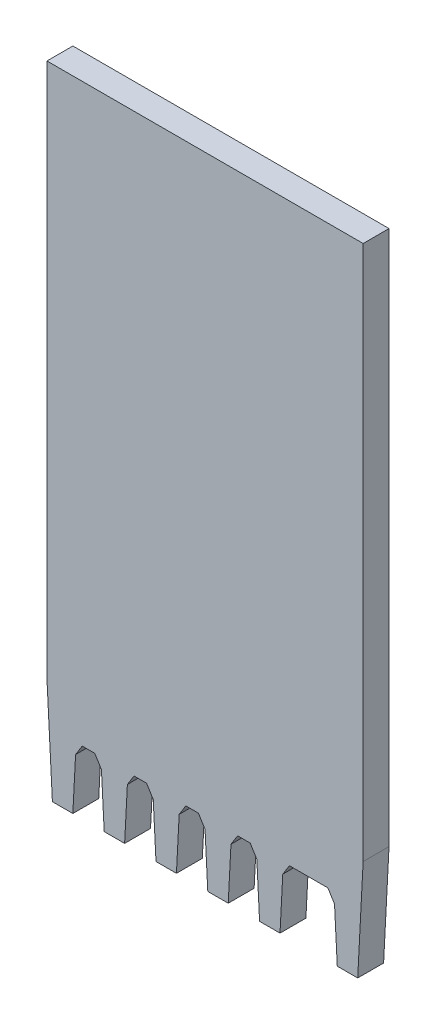
SolidWorks part; units mm, degrees
ref_plane "Front Plane" through (0, 0, 0) normal (0, 0, 1) x (1, 0, 0)
ref_plane "Top Plane" through (0, 0, 0) normal (0, 1, 0) x (1, 0, 0)
ref_plane "Right Plane" through (0, 0, 0) normal (1, 0, 0) x (0, 0, -1)
sketch "Sketch1" plane through (0, 0, 0) normal (0, 0, 1) x (1, 0, 0)
  line L0 (0, 0) -> (0, 37) construction
  line L1 (0, 37) -> (18.3124, 37) construction
  line L2 (18.3124, 37) -> (18.3124, 0) construction
  line L3 (18.3124, 0) -> (0, 0) construction
  line L4 (0, 3) -> (18.3124, 3) construction
  line L5 (0, 6) -> (18.3124, 6) construction
  line L6 (0.9062, 6) -> (0.9062, 0) construction
  line L7 (3.9062, 6) -> (3.9062, 0) construction
  line L8 (6.9062, 6) -> (6.9062, 0) construction
  line L9 (9.9062, 6) -> (9.9062, 0) construction
  line L10 (12.9062, 6) -> (12.9062, 0) construction
  line L11 (17.4062, 6) -> (17.4062, 0) construction
  line L12 (0.9062, 3) -> (3.9062, 3) construction
  line L13 (3.9062, 3) -> (6.9062, 3) construction
  line L14 (6.9062, 3) -> (9.9062, 3) construction
  line L15 (9.9062, 3) -> (12.9062, 3) construction
  line L16 (12.9062, 3) -> (17.4062, 3) construction
  line L17 (0.9062, 3) -> (0, 3) construction
  line L18 (17.4062, 3) -> (18.3124, 3) construction
  line L19 (2.4062, 3) -> (2.4062, 0) construction
  line L20 (5.4062, 3) -> (5.4062, 0) construction
  line L21 (8.4062, 3) -> (8.4062, 0) construction
  line L22 (11.4062, 3) -> (11.4062, 0) construction
  line L23 (15.1562, 3) -> (15.1562, 0) construction
  line L24 (14.4062, 3.75) -> (15.9062, 3.75) construction
  line L25 (0, 6) -> (0.3144, 0)
  line L26 (0.3144, 0) -> (1.4979, 0)
  line L27 (1.4979, 0) -> (1.6572, 3.0393)
  line L28 (3.1552, 3.0393) -> (3.3144, 0)
  line L29 (3.3144, 0) -> (4.4979, 0)
  line L30 (4.4979, 0) -> (4.6572, 3.0393)
  line L31 (6.1552, 3.0393) -> (6.3144, 0)
  line L32 (6.3144, 0) -> (7.4979, 0)
  line L33 (7.4979, 0) -> (7.6572, 3.0393)
  line L34 (9.1552, 3.0393) -> (9.3144, 0)
  line L35 (9.3144, 0) -> (10.4979, 0)
  line L36 (10.4979, 0) -> (10.6572, 3.0393)
  line L37 (12.1552, 3.0393) -> (12.3144, 0)
  line L38 (12.3144, 0) -> (13.4979, 0)
  line L39 (13.4979, 0) -> (13.6572, 3.0393)
  line L40 (16.6552, 3.0393) -> (16.8144, 0)
  line L41 (16.8144, 0) -> (17.9979, 0)
  line L42 (17.9979, 0) -> (18.3124, 6)
  line L44 (1.6572, 3.0393) -> (2.0426, 3.656)
  line L45 (0, 6) -> (0, 37)
  line L46 (0, 37) -> (18.3124, 37)
  line L47 (18.3124, 37) -> (18.3124, 6)
  line L48 (9.1562, 37) -> (9.1562, 6) construction
  line L49 (2.0426, 3.656) -> (2.7698, 3.656)
  line L50 (2.7698, 3.656) -> (3.1552, 3.0393)
  line L51 (4.6572, 3.0393) -> (5.0426, 3.656)
  line L52 (5.0426, 3.656) -> (5.7698, 3.656)
  line L53 (5.7698, 3.656) -> (6.1552, 3.0393)
  line L54 (7.6572, 3.0393) -> (8.0426, 3.656)
  line L55 (8.0426, 3.656) -> (8.7698, 3.656)
  line L56 (8.7698, 3.656) -> (9.1552, 3.0393)
  line L57 (10.6572, 3.0393) -> (11.0426, 3.656)
  line L58 (11.0426, 3.656) -> (11.7698, 3.656)
  line L59 (11.7698, 3.656) -> (12.1552, 3.0393)
  line L60 (13.6572, 3.0393) -> (14.0426, 3.656)
  line L61 (14.0426, 3.656) -> (16.2698, 3.656)
  line L62 (16.2698, 3.656) -> (16.6552, 3.0393)
  arc A0 (3.1552, 3.0393) -> (1.6572, 3.0393) centre (2.4062, 3) ccw construction
  arc A1 (6.1552, 3.0393) -> (4.6572, 3.0393) centre (5.4062, 3) ccw construction
  arc A2 (9.1552, 3.0393) -> (7.6572, 3.0393) centre (8.4062, 3) ccw construction
  arc A3 (12.1552, 3.0393) -> (10.6572, 3.0393) centre (11.4062, 3) ccw construction
  arc A4 (13.6572, 3.0393) -> (14.4062, 3.75) centre (14.4062, 3) cw construction
  arc A5 (16.6552, 3.0393) -> (15.9062, 3.75) centre (15.9062, 3) ccw construction
  dimension "D7" = 0.75
  dimension "D1" = 3
  dimension "D2" = 6
  dimension "D3" = 31
  dimension "D4" = 3
  dimension "D6" = 4.5
  dimension "D8" = 3
  dimension "D9" = 18.3124
  dimension "D10" = 37
extrude "Boss-Extrude1" add sketch "Sketch1" along normal blind 1.5
sketch "Sketch3" plane through (0, 0, 0) normal (0, 0, 1) x (1, 0, 0)
  line L0 (-0.4005, 6) -> (18.7129, 6)
  line L1 (18.7129, 3) -> (-0.4005, 3) construction
  line L2 (-0.4005, 0) -> (18.7129, 0) construction
  line L3 (-0.4005, -0.5) -> (18.7129, -0.5) construction
  line L4 (18.7129, -0.5) -> (18.7129, 6) construction
  line L5 (-0.4005, 6) -> (-0.4005, -0.5) construction
  line L6 (18.3124, 0) -> (0, 0) construction
  line L7 (0, 3) -> (18.3124, 3) construction
  line L8 (0, 6) -> (18.3124, 6) construction
  line L9 (0.3407, -0.5) -> (0, 6) construction
  line L10 (18.3124, 6) -> (17.9717, -0.5) construction
  line L11 (17.9979, 0) -> (18.3124, 6) construction
  line L12 (0, 6) -> (0.3144, 0) construction
  line L13 (5.4062, 6) -> (5.4062, -0.5) construction
  line L14 (3.9062, 6) -> (3.9062, -0.5) construction
  line L15 (5.4062, 3) -> (5.4062, 0) construction
  line L16 (3.1572, 3) -> (3.3407, -0.5) construction
  line L17 (2.7567, 3) -> (2.9401, -0.5)
  line L18 (3.1552, 3.0393) -> (3.3144, 0) construction
  line L19 (2.9401, -0.5) -> (4.8723, -0.5)
  line L20 (4.8723, -0.5) -> (5.0557, 3)
  line L21 (2.8484, 1.25) -> (3.2478, 1.2709) construction
  line L22 (5.9401, -0.5) -> (5.7567, 3)
  line L26 (7.8723, -0.5) -> (5.9401, -0.5)
  line L27 (8.0557, 3) -> (7.8723, -0.5)
  line L30 (2.4062, -0.5) -> (2.4062, 6) construction
  line L31 (2.4062, 3) -> (2.4062, 0) construction
  line L32 (8.4062, 6) -> (8.4062, -0.5) construction
  line L34 (11.4062, -0.5) -> (11.4062, 6) construction
  line L35 (15.1562, -0.5) -> (15.1562, 6) construction
  line L36 (8.4062, 3) -> (8.4062, 0) construction
  line L37 (11.4062, 3) -> (11.4062, 0) construction
  line L38 (15.1562, 3) -> (15.1562, 0) construction
  line L39 (10.8723, -0.5) -> (11.0557, 3)
  line L40 (8.9401, -0.5) -> (10.8723, -0.5)
  line L41 (8.7567, 3) -> (8.9401, -0.5)
  line L42 (11.9401, -0.5) -> (11.7567, 3)
  line L43 (13.8723, -0.5) -> (11.9401, -0.5)
  line L44 (14.0557, 3) -> (13.8723, -0.5)
  line L45 (16.4401, -0.5) -> (18.3723, -0.5)
  line L46 (16.2567, 3) -> (16.4401, -0.5)
  line L47 (18.3723, -0.5) -> (18.7129, 6)
  line L48 (1.8723, -0.5) -> (-0.0599, -0.5)
  line L49 (2.0557, 3) -> (1.8723, -0.5)
  line L50 (-0.0599, -0.5) -> (-0.4005, 6)
  line L51 (16.2567, 3) -> (14.0557, 3)
  line L52 (11.7567, 3) -> (11.0557, 3)
  line L53 (8.7567, 3) -> (8.0557, 3)
  line L54 (5.7567, 3) -> (5.0557, 3)
  line L55 (2.7567, 3) -> (2.0557, 3)
  dimension "D1" = 0.5
  dimension "D2" = 0.4
ref_plane "Plane1" through (3.9062, 0, 0) normal (1, 0, 0) x (0, 0, -1)
sketch "Sketch4" plane through (3.9062, 0, 0) normal (1, 0, 0) x (0, 0, -1)
  line L0 (0, 6) -> (0, -0.5) construction
  line L1 (0.6, 6) -> (-2.1, 6) construction
  line L2 (0.6, 6) -> (0.6, -0.5) construction
  line L3 (0.6, -0.5) -> (-2.1, -0.5) construction
  line L4 (-2.1, 6) -> (-2.1, -0.5) construction
  line L5 (-0.75, -0.5) -> (-0.75, 6) construction
  line L6 (-1.5, 6) -> (-1.5, -0.5) construction
  line L7 (0.6, 2.4005) -> (-2.1, 2.4005) construction
  line L8 (0.3, 6) -> (0.3, -0.5) construction
  line L9 (0.6, 2.4005) -> (3.846, 6) construction
  line L10 (2.2302, 6) -> (0.6, 4.1923) construction
  line L11 (0.6, 4.1923) -> (1.7139, 3.1878) construction
  line L12 (1.7139, 3.1878) -> (4.25, 6)
  line L13 (4.25, 6) -> (0.6, 6) construction
  line L14 (0.3, 1) -> (-1.8, 1) construction
  line L15 (-2.1, 0) -> (0.6, 0) construction
  line L16 (1.7139, 3.1878) -> (1.4912, 3.3887)
  line L17 (1.4912, 3.3887) -> (0.6, 2.4005)
  line L18 (-3.2139, 3.1878) -> (-5.75, 6)
  line L19 (-3.2139, 3.1878) -> (-2.9912, 3.3887)
  line L20 (-2.9912, 3.3887) -> (-2.1, 2.4005)
  line L21 (-2.1, 6) -> (-5.75, 6) construction
  line L22 (0.6, 3.0724) -> (3.2401, 6) construction
  arc A0 (0.4965, 2.2224) -> (0.6, -0.5) centre (4.2, 1) ccw
  arc A1 (0.6, 2.4005) -> (0.4965, 2.2224) centre (0.9713, 2.0656) ccw
  arc A2 (-2.1, 2.4005) -> (-1.9965, 2.2224) centre (-2.4713, 2.0656) cw
  arc A3 (-1.9965, 2.2224) -> (-2.1, -0.5) centre (-5.7, 1) cw
  dimension "D6" = 0.5
  dimension "D1" = 0.6
  dimension "D2" = 0.3
  dimension "D3" = 1.5
  dimension "D4" = 1
  dimension "D5" = 0.3
  dimension "D7" = 10
sketch "Sketch5" plane through (0, 0, 0) normal (1, 0, 0) x (0, 0, -1)
  line L0 (2.2302, 6) -> (0.6, 4.1923) construction
  line L1 (0.6, 4.1923) -> (1.7139, 3.1878) construction
  line L2 (1.7139, 3.1878) -> (4.25, 6) construction
  line L3 (2.2302, 6) -> (0.6, 4.1923) construction
  line L4 (0.6, 4.1923) -> (1.7139, 3.1878) construction
  line L5 (1.7139, 3.1878) -> (4.25, 6) construction
ref_plane "Plane2" through (0, 2.6105, -2.3541) normal (0, 0.7426, -0.6697) x (1, 0, 0)
sketch "Sketch6" plane through (0, 2.6105, -2.3541) normal (0, 0.7426, -0.6697) x (1, 0, 0)
  line L1 (3.9062, -2.362) -> (3.9062, -0.862) construction
  line L2 (3.9062, -2.362) -> (3.9062, -5.0612) construction
  line L3 (4.6562, -5.0612) -> (3.1562, -5.0612)
  line L4 (4.6562, -1.612) -> (3.1562, -1.612) construction
  line L5 (3.1562, -1.612) -> (3.1562, -5.0612)
  line L6 (4.6562, -1.612) -> (4.6562, -5.0612)
  line L10 (2.4062, -5.0612) -> (15.1562, -5.0612) construction
  line L11 (15.1562, -5.0612) -> (15.1562, -0.862) construction
  line L12 (15.1562, -0.862) -> (2.4062, -0.862) construction
  line L13 (2.4062, -0.862) -> (2.4062, -5.0612) construction
  line L14 (15.1562, 0.3349) -> (15.1562, -4.0182) construction
  line L15 (2.4062, 0.3349) -> (2.4062, -4.0182) construction
  line L16 (11.4062, -5.0612) -> (11.4062, -0.862) construction
  line L17 (8.4062, -5.0612) -> (8.4062, -0.862) construction
  line L18 (5.4062, -5.0612) -> (5.4062, -0.862) construction
  line L19 (5.4062, -4.0182) -> (5.4062, 0.3349) construction
  line L20 (8.4062, -4.0182) -> (8.4062, 0.3349) construction
  line L21 (11.4062, 0.3349) -> (11.4062, -4.0182) construction
  line L22 (0.1562, -1.612) -> (0.1562, -5.0612)
  line L23 (0.1562, -5.0612) -> (1.6562, -5.0612)
  line L24 (1.6562, -1.612) -> (1.6562, -5.0612)
  line L25 (7.6562, -1.612) -> (7.6562, -5.0612)
  line L26 (6.1562, -5.0612) -> (7.6562, -5.0612)
  line L27 (6.1562, -1.612) -> (6.1562, -5.0612)
  line L28 (10.6562, -1.612) -> (10.6562, -5.0612)
  line L29 (10.6562, -5.0612) -> (9.1562, -5.0612)
  line L30 (9.1562, -1.612) -> (9.1562, -5.0612)
  line L31 (13.6562, -1.612) -> (13.6562, -5.0612)
  line L32 (12.1562, -5.0612) -> (13.6562, -5.0612)
  line L33 (12.1562, -1.612) -> (12.1562, -5.0612)
  line L34 (18.1562, -1.612) -> (18.1562, -5.0612)
  line L35 (18.1562, -5.0612) -> (16.6562, -5.0612)
  line L36 (16.6562, -1.612) -> (16.6562, -5.0612)
  circle A0 centre (3.9062, -1.612) radius 0.75 construction
  arc A1 (4.6562, -1.612) -> (3.1562, -1.612) centre (3.9062, -1.612) ccw
  arc A2 (0.1562, -1.612) -> (1.6562, -1.612) centre (0.9062, -1.612) cw
  arc A3 (6.1562, -1.612) -> (7.6562, -1.612) centre (6.9062, -1.612) cw
  arc A4 (10.6562, -1.612) -> (9.1562, -1.612) centre (9.9062, -1.612) ccw
  arc A5 (12.1562, -1.612) -> (13.6562, -1.612) centre (12.9062, -1.612) cw
  arc A6 (18.1562, -1.612) -> (16.6562, -1.612) centre (17.4062, -1.612) ccw
ref_plane "Plane3" through (0, 1.6223, -1.463) normal (0, 0.7426, -0.6697) x (1, 0, 0)
sketch "Sketch7" plane through (0, 1.6223, -1.463) normal (0, 0.7426, -0.6697) x (1, 0, 0)
  line L0 (3.1562, -1.612) -> (3.1562, -5.0612) construction
  line L1 (4.6562, -5.0612) -> (3.1562, -5.0612) construction
  line L2 (4.6562, -1.612) -> (4.6562, -5.0612) construction
  line L3 (3.1562, -1.612) -> (3.1562, -5.0612) construction
  line L4 (4.6562, -5.0612) -> (3.1562, -5.0612) construction
  line L5 (4.6562, -1.612) -> (4.6562, -5.0612) construction
  line L6 (3.9062, -0.862) -> (3.9062, -5.0612) construction
  line L7 (4.6562, -1.612) -> (3.1562, -1.612) construction
  line L8 (4.6562, -2.362) -> (3.1562, -2.362) construction
  line L9 (3.4562, -1.612) -> (3.4562, -2.362)
  line L10 (3.4562, -2.362) -> (4.3562, -2.362)
  line L11 (4.3562, -2.362) -> (4.3562, -1.612)
  line L12 (2.4062, -0.862) -> (2.4062, -5.0612) construction
  line L13 (2.4062, -5.0612) -> (15.1562, -5.0612) construction
  line L14 (15.1562, -0.862) -> (2.4062, -0.862) construction
  line L15 (5.4062, -5.0612) -> (5.4062, -0.862) construction
  line L16 (8.4062, -5.0612) -> (8.4062, -0.862) construction
  line L17 (11.4062, -5.0612) -> (11.4062, -0.862) construction
  line L18 (15.1562, -5.0612) -> (15.1562, -0.862) construction
  line L19 (2.4062, -0.862) -> (2.4062, -5.0612) construction
  line L20 (2.4062, -5.0612) -> (15.1562, -5.0612) construction
  line L21 (15.1562, -0.862) -> (2.4062, -0.862) construction
  line L22 (5.4062, -5.0612) -> (5.4062, -0.862) construction
  line L23 (8.4062, -5.0612) -> (8.4062, -0.862) construction
  line L24 (11.4062, -5.0612) -> (11.4062, -0.862) construction
  line L25 (15.1562, -5.0612) -> (15.1562, -0.862) construction
  line L26 (0.4562, -2.362) -> (0.4562, -1.612)
  line L27 (1.3562, -2.362) -> (0.4562, -2.362)
  line L28 (1.3562, -1.612) -> (1.3562, -2.362)
  line L29 (7.3562, -2.362) -> (6.4562, -2.362)
  line L30 (7.3562, -1.612) -> (7.3562, -2.362)
  line L31 (6.4562, -2.362) -> (6.4562, -1.612)
  line L32 (9.4562, -1.612) -> (9.4562, -2.362)
  line L33 (10.3562, -2.362) -> (10.3562, -1.612)
  line L34 (9.4562, -2.362) -> (10.3562, -2.362)
  line L35 (13.3562, -1.612) -> (13.3562, -2.362)
  line L36 (12.4562, -2.362) -> (12.4562, -1.612)
  line L37 (13.3562, -2.362) -> (12.4562, -2.362)
  line L38 (16.9562, -1.612) -> (16.9562, -2.362)
  line L39 (17.8562, -2.362) -> (17.8562, -1.612)
  line L40 (16.9562, -2.362) -> (17.8562, -2.362)
  arc A0 (4.6562, -1.612) -> (3.1562, -1.612) centre (3.9062, -1.612) ccw construction
  arc A1 (4.6562, -1.612) -> (3.1562, -1.612) centre (3.9062, -1.612) ccw construction
  circle A2 centre (3.9062, -1.612) radius 0.45 construction
  arc A3 (4.3562, -1.612) -> (3.4562, -1.612) centre (3.9062, -1.612) ccw
  arc A4 (0.4562, -1.612) -> (1.3562, -1.612) centre (0.9062, -1.612) cw
  arc A5 (6.4562, -1.612) -> (7.3562, -1.612) centre (6.9062, -1.612) cw
  arc A6 (10.3562, -1.612) -> (9.4562, -1.612) centre (9.9062, -1.612) ccw
  arc A7 (12.4562, -1.612) -> (13.3562, -1.612) centre (12.9062, -1.612) cw
  arc A8 (17.8562, -1.612) -> (16.9562, -1.612) centre (17.4062, -1.612) ccw
ref_plane "bisect" through (0, 0, 0.75) normal (0, 0, 1) x (1, 0, 0)
ref_plane "insert_surface" through (0, 6, 0) normal (0, 1, 0) x (1, 0, 0)
sketch "Sketch8" plane through (0, 6, 0) normal (0, 1, 0) x (1, 0, 0)
  line L0 (18.7129, -0.75) -> (-0.4005, -0.75) construction
  line L1 (-0.4005, 0.6) -> (18.7129, 0.6)
  line L2 (-0.4005, 0.6) -> (-0.4005, -2.1)
  line L3 (-0.4005, -2.1) -> (18.7129, -2.1)
  line L4 (18.7129, 0.6) -> (18.7129, -2.1)
  line L5 (9.1562, 0.6) -> (9.1562, -2.1) construction
  line L6 (0, 0) -> (18.3124, 0) construction
  line L7 (0, 0) -> (0, -1.5) construction
  line L8 (0, -1.5) -> (18.3124, -1.5) construction
  line L9 (18.3124, 0) -> (18.3124, -1.5) construction
  line L10 (18.7129, 0.3) -> (-0.4005, 0.3) construction
  line L11 (18.7129, -1.8) -> (-0.4005, -1.8) construction
sketch "Sketch9" plane through (0, 0, 0) normal (0, 0, 1) x (1, 0, 0)
  line L0 (18.3723, -0.5) -> (18.7129, 6) construction
  line L1 (-0.4005, 6) -> (18.7129, 6) construction
  line L2 (-0.0599, -0.5) -> (-0.4005, 6) construction
  line L3 (1.8723, -0.5) -> (-0.0599, -0.5) construction
  line L4 (2.0557, 3) -> (1.8723, -0.5) construction
  line L5 (2.7567, 3) -> (2.0557, 3) construction
  line L6 (2.7567, 3) -> (2.9401, -0.5) construction
  line L7 (2.9401, -0.5) -> (4.8723, -0.5) construction
  line L8 (4.8723, -0.5) -> (5.0557, 3) construction
  line L9 (5.7567, 3) -> (5.0557, 3) construction
  line L10 (5.9401, -0.5) -> (5.7567, 3) construction
  line L11 (7.8723, -0.5) -> (5.9401, -0.5) construction
  line L12 (8.0557, 3) -> (7.8723, -0.5) construction
  line L13 (8.7567, 3) -> (8.0557, 3) construction
  line L14 (8.7567, 3) -> (8.9401, -0.5) construction
  line L15 (8.9401, -0.5) -> (10.8723, -0.5) construction
  line L16 (10.8723, -0.5) -> (11.0557, 3) construction
  line L17 (11.7567, 3) -> (11.0557, 3) construction
  line L18 (11.9401, -0.5) -> (11.7567, 3) construction
  line L19 (13.8723, -0.5) -> (11.9401, -0.5) construction
  line L20 (14.0557, 3) -> (13.8723, -0.5) construction
  line L21 (16.2567, 3) -> (14.0557, 3) construction
  line L22 (16.2567, 3) -> (16.4401, -0.5) construction
  line L23 (16.4401, -0.5) -> (18.3723, -0.5) construction
  line L24 (18.3723, -0.5) -> (18.7129, 6)
  line L25 (-0.4005, 6) -> (18.7129, 6) construction
  line L26 (-0.0599, -0.5) -> (-0.4005, 6)
  line L27 (1.8723, -0.5) -> (-0.0599, -0.5)
  line L28 (2.0557, 3) -> (1.8723, -0.5)
  line L29 (2.7567, 3) -> (2.0557, 3) construction
  line L30 (2.7567, 3) -> (2.9401, -0.5)
  line L31 (2.9401, -0.5) -> (4.8723, -0.5)
  line L32 (4.8723, -0.5) -> (5.0557, 3)
  line L33 (5.7567, 3) -> (5.0557, 3) construction
  line L34 (5.9401, -0.5) -> (5.7567, 3)
  line L35 (7.8723, -0.5) -> (5.9401, -0.5)
  line L36 (8.0557, 3) -> (7.8723, -0.5)
  line L37 (8.7567, 3) -> (8.0557, 3) construction
  line L38 (8.7567, 3) -> (8.9401, -0.5)
  line L39 (8.9401, -0.5) -> (10.8723, -0.5)
  line L40 (10.8723, -0.5) -> (11.0557, 3)
  line L41 (11.7567, 3) -> (11.0557, 3) construction
  line L42 (11.9401, -0.5) -> (11.7567, 3)
  line L43 (13.8723, -0.5) -> (11.9401, -0.5)
  line L44 (14.0557, 3) -> (13.8723, -0.5)
  line L45 (16.2567, 3) -> (14.0557, 3) construction
  line L46 (16.2567, 3) -> (16.4401, -0.5)
  line L47 (16.4401, -0.5) -> (18.3723, -0.5)
  line L48 (16.2567, 3) -> (16.2567, 6)
  line L49 (14.0557, 3) -> (14.0557, 6)
  line L50 (11.7567, 3) -> (11.7567, 6)
  line L51 (18.7129, 6) -> (-0.4005, 6) construction
  line L52 (11.0557, 3) -> (11.0557, 6)
  line L53 (-0.4005, 6) -> (18.7129, 6) construction
  line L54 (8.7567, 3) -> (8.7567, 6)
  line L55 (8.0557, 3) -> (8.0557, 6)
  line L58 (5.7567, 3) -> (5.7567, 6)
  line L60 (5.0557, 3) -> (5.0557, 6)
  line L62 (15.1562, -0.5) -> (15.1562, 6) construction
  line L63 (15.1562, -0.5) -> (15.1562, 6) construction
  line L64 (2.7567, 3) -> (2.7567, 6)
  line L65 (2.0557, 3) -> (2.0557, 6)
  line L67 (18.7129, 6) -> (16.2567, 6)
  line L68 (14.0557, 6) -> (11.7567, 6)
  line L69 (11.0557, 6) -> (8.7567, 6)
  line L70 (8.0557, 6) -> (5.7567, 6)
  line L71 (5.0557, 6) -> (2.7567, 6)
  line L72 (2.0557, 6) -> (-0.4005, 6)
sketch "Sketch10" plane through (0, 6, 0) normal (0, 1, 0) x (1, 0, 0)
  line L0 (9.1562, -5.75) -> (9.1562, -0.75) construction
  line L1 (-0.8438, 4.25) -> (19.1562, 4.25)
  line L2 (-0.8438, 4.25) -> (-0.8438, -5.75)
  line L3 (-0.8438, -5.75) -> (19.1562, -5.75)
  line L4 (19.1562, 4.25) -> (19.1562, -5.75)
  line L5 (9.1562, -0.75) -> (9.1562, 4.25) construction
  line L6 (9.1562, -0.75) -> (19.1562, -0.75) construction
  line L7 (9.1562, -0.75) -> (-0.8438, -0.75) construction
  line L8 (-10.5124, -0.75) -> (10.5124, -0.75) construction
  dimension "D1" = 10
  dimension "D2" = 20
